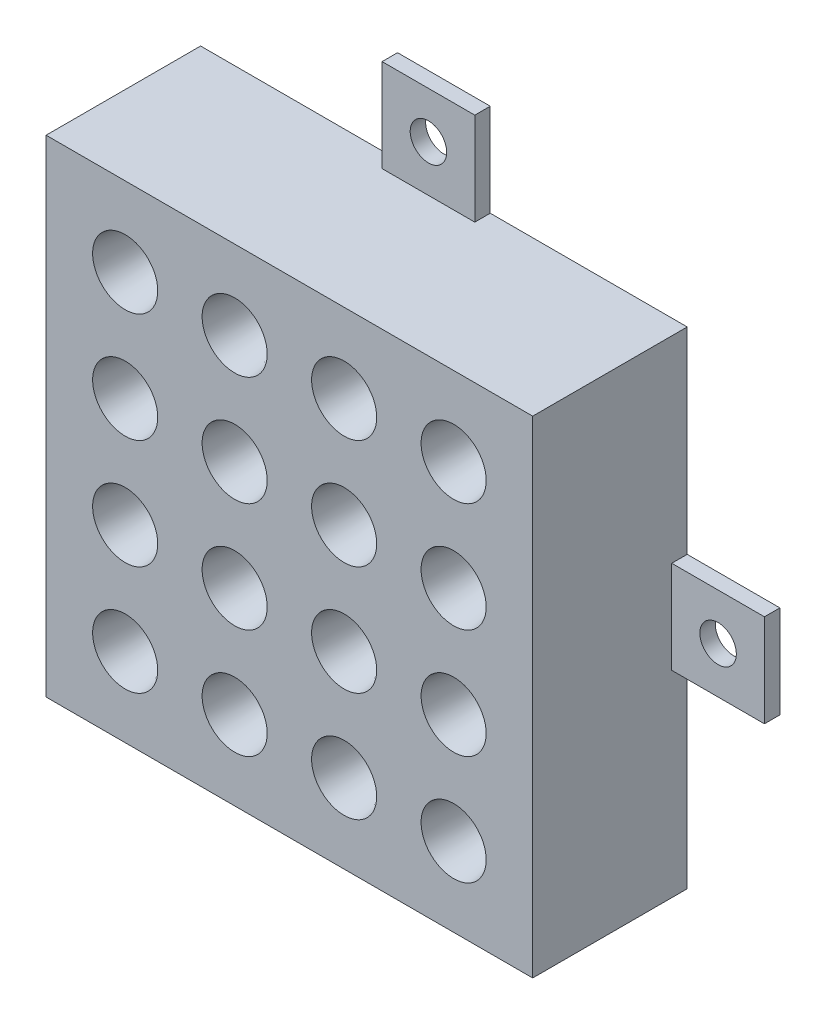
SolidWorks part; units mm, degrees
ref_plane "Front Plane" through (0, 0, 0) normal (0, 0, 1) x (1, 0, 0)
ref_plane "Top Plane" through (0, 0, 0) normal (0, 1, 0) x (1, 0, 0)
ref_plane "Right Plane" through (0, 0, 0) normal (1, 0, 0) x (0, 0, -1)
sketch "Sketch1" plane through (0, 0, 0) normal (0, 0, 1) x (1, 0, 0)
  line L1 (-52.4737, 14.5622) -> (-12.4737, 14.5622)
  line L2 (-52.4737, 14.5622) -> (-52.4737, -25.4378)
  line L3 (-52.4737, -25.4378) -> (-12.4737, -25.4378)
  line L4 (-12.4737, 14.5622) -> (-12.4737, -25.4378)
  dimension "D1" = 40
  dimension "D2" = 40
extrude "Boss-Extrude1" add sketch "Sketch1" along normal blind 12.7
sketch "Sketch2" plane through (0, 0, 12.7) normal (0, 0, 1) x (1, 0, 0)
  line L0 (-12.4737, 14.5622) -> (-52.4737, 14.5622) construction
  line L1 (-52.4737, 14.5622) -> (-52.4737, -25.4378) construction
  circle A0 centre (-45.9737, 8.0622) radius 2.6756
  circle A1 centre (-36.9737, 8.0622) radius 2.6756
  circle A2 centre (-27.9737, 8.0622) radius 2.6756
  circle A3 centre (-18.9737, 8.0622) radius 2.6756
  circle A4 centre (-45.9737, -0.9378) radius 2.6756
  circle A5 centre (-36.9737, -0.9378) radius 2.6756
  circle A6 centre (-27.9737, -0.9378) radius 2.6756
  circle A7 centre (-18.9737, -0.9378) radius 2.6756
  circle A8 centre (-45.9737, -9.9378) radius 2.6756
  circle A9 centre (-36.9737, -9.9378) radius 2.6756
  circle A10 centre (-27.9737, -9.9378) radius 2.6756
  circle A11 centre (-18.9737, -9.9378) radius 2.6756
  circle A12 centre (-45.9737, -18.9378) radius 2.6756
  circle A13 centre (-36.9737, -18.9378) radius 2.6756
  circle A14 centre (-27.9737, -18.9378) radius 2.6756
  circle A15 centre (-18.9737, -18.9378) radius 2.6756
  dimension "D1" = 5.3512
  dimension "D2" = 6.5
  dimension "D5" = 6.5
  dimension "D6" = 9
  dimension "D3" = 4
  dimension "D4" = 4
extrude "Cut-Extrude1" cut sketch "Sketch2" against normal blind 11.176 draft 8.75
sketch "Sketch3" plane through (0, 14.5622, 0) normal (0, 1, 0) x (1, 0, 0)
  line L0 (-12.4737, 0) -> (-52.4737, 0) construction
  line L1 (-36.2837, 0) -> (-28.6637, 0)
  line L2 (-36.2837, 0) -> (-36.2837, -1.27)
  line L3 (-36.2837, -1.27) -> (-28.6637, -1.27)
  line L4 (-28.6637, 0) -> (-28.6637, -1.27)
  line L7 (-12.4737, -12.7) -> (-12.4737, 0) construction
  dimension "D1" = 1.27
  dimension "D2" = 7.62
  dimension "D3" = 16.19
extrude "Boss-Extrude2" add sketch "Sketch3" along normal blind 7.62
sketch "Sketch4" plane through (-12.4737, 0, 0) normal (1, 0, 0) x (0, 0, -1)
  line L0 (0, -25.4378) -> (0, 14.5622) construction
  line L1 (-1.27, -1.6278) -> (0, -1.6278)
  line L2 (-1.27, -1.6278) -> (-1.27, -9.2478)
  line L3 (-1.27, -9.2478) -> (0, -9.2478)
  line L4 (0, -1.6278) -> (0, -9.2478)
  dimension "D1" = 7.62
  dimension "D2" = 16.19
  dimension "D3" = 1.27
extrude "Boss-Extrude3" add sketch "Sketch4" along normal blind 7.62
sketch "Sketch5" plane through (-52.4737, 0, 0) normal (-1, 0, 0) x (0, 0, 1)
  line L0 (0, 14.5622) -> (0, -25.4378) construction
  line L1 (1.27, -1.6277) -> (0, -1.6277)
  line L2 (1.27, -1.6277) -> (1.27, -9.2477)
  line L3 (1.27, -9.2477) -> (0, -9.2477)
  line L4 (0, -1.6277) -> (0, -9.2477)
  dimension "D1" = 16.19
  dimension "D2" = 7.62
  dimension "D3" = 1.27
extrude "Boss-Extrude4" add sketch "Sketch5" along normal blind 7.62
sketch "Sketch6" plane through (0, -25.4378, 0) normal (0, -1, 0) x (1, 0, 0)
  line L0 (-52.4737, 0) -> (-12.4737, 0) construction
  line L1 (-36.2838, 1.27) -> (-28.6638, 1.27)
  line L2 (-36.2838, 1.27) -> (-36.2838, 0)
  line L3 (-36.2838, 0) -> (-28.6638, 0)
  line L4 (-28.6638, 1.27) -> (-28.6638, 0)
  dimension "D1" = 7.62
  dimension "D2" = 16.19
  dimension "D3" = 1.27
extrude "Boss-Extrude5" add sketch "Sketch6" along normal blind 7.62
sketch "Sketch7" plane through (0, 0, 1.27) normal (0, 0, 1) x (1, 0, 0)
  line L0 (-28.6638, -33.0578) -> (-28.6638, -25.4378) construction
  line L1 (-28.6638, -33.0578) -> (-36.2838, -33.0578) construction
  line L2 (-60.0937, -9.2477) -> (-52.4737, -9.2477) construction
  line L3 (-60.0937, -9.2477) -> (-60.0937, -1.6277) construction
  line L4 (-4.8537, -9.2478) -> (-12.4737, -9.2478) construction
  line L5 (-4.8537, -1.6278) -> (-4.8537, -9.2478) construction
  line L6 (-36.2837, 22.1822) -> (-28.6637, 22.1822) construction
  line L7 (-28.6637, 22.1822) -> (-28.6637, 14.5622) construction
  circle A0 centre (-32.4738, -29.2478) radius 1.5
  circle A1 centre (-56.2837, -5.4377) radius 1.5
  circle A2 centre (-8.6637, -5.4378) radius 1.5
  circle A3 centre (-32.4737, 18.3722) radius 1.5
  dimension "D1" = 3
  dimension "D4" = 3
  dimension "D7" = 3
  dimension "D10" = 3.81
  dimension "D12" = 3
  dimension "D2" = 3.81
  dimension "D3" = 3.81
  dimension "D5" = 3.81
  dimension "D6" = 3.81
  dimension "D8" = 3.81
  dimension "D9" = 3.81
  dimension "D11" = 3.81
  dimension "D13" = 47.62
  dimension "D14" = 47.62
extrude "M3 diameter holes" cut sketch "Sketch7" against normal blind 7.62 contours A0 | A2 | A1 | A3
sketch "Sketch8" plane through (0, -25.4378, 0) normal (0, -1, 0) x (1, 0, 0)
  line L2 (-28.6638, 0) -> (-12.4737, 0) construction
  line L4 (-52.4737, 12.7) -> (-52.4737, 0) construction
  circle A0 centre (-41.4737, 5) radius 0.4572
  circle A1 centre (-41.4737, 5) radius 0.0267
  dimension "D1" = 0.9144
  dimension "D4" = 0.0533
  dimension "D2" = 5
  dimension "D3" = 11
ref_axis "Axis1" through (-41.4737, -25.4378, 5) along (0, -1, 0)
ref_plane "Plane1" through (-41.4737, 0, 0) normal (1, 0, 0) x (0, 0, -1)
sketch "Sketch10" plane through (-41.4737, 0, 0) normal (1, 0, 0) x (0, 0, -1)
  line L0 (-5, -25.4378) -> (-6.3397, -20.4378)
  line L1 (-5.4572, -25.4378) -> (-4.5428, -25.4378) construction
  line L2 (0, -25.4378) -> (0, -9.2478) construction
  dimension "D1" = 5
  dimension "D2" = 15
ref_plane "Plane3" through (-41.4737, -25.4378, 5) normal (0, 0.9659, 0.2588) x (-1, 0, 0)
hole_wizard "Ø1.0 (1) Diameter Hole1" positions "Sketch16" profile "Sketch15" hole size "Ø1.0" standard "Ansi Metric"
sketch "Sketch16" plane through (-41.4737, -25.4378, 5) normal (0, 0.9659, 0.2588) x (-1, 0, 0)
  point P0 (0, 0)
  dimension "D1" = 0
sketch "Sketch15" plane through (-41.4737, -25.4378, 5) normal (1, 0, 0) x (0, 0.2588, -0.9659)
  line L0 (0, 0) -> (0, 5.3004)
  line L1 (0, 5.3004) -> (0.5, 5)
  line L2 (0.5, 5) -> (0.5, 0)
  line L5 (0.5, 0) -> (0, 0)
  line L10 (0, 5.3004) -> (-0.5, 5) construction
  line L11 (0, -6.35) -> (0, 107.95) construction
  dimension "Hole Dia." = 1
  dimension "Hole Depth" = 5
  dimension "Drill Angle" = 118
extrude "Cut-Extrude3" cut sketch "Sketch8" along direction (0, 0.9659, 0.2588) on the side against the normal blind 2
equation "\"D3@Sketch8\" = 11"
